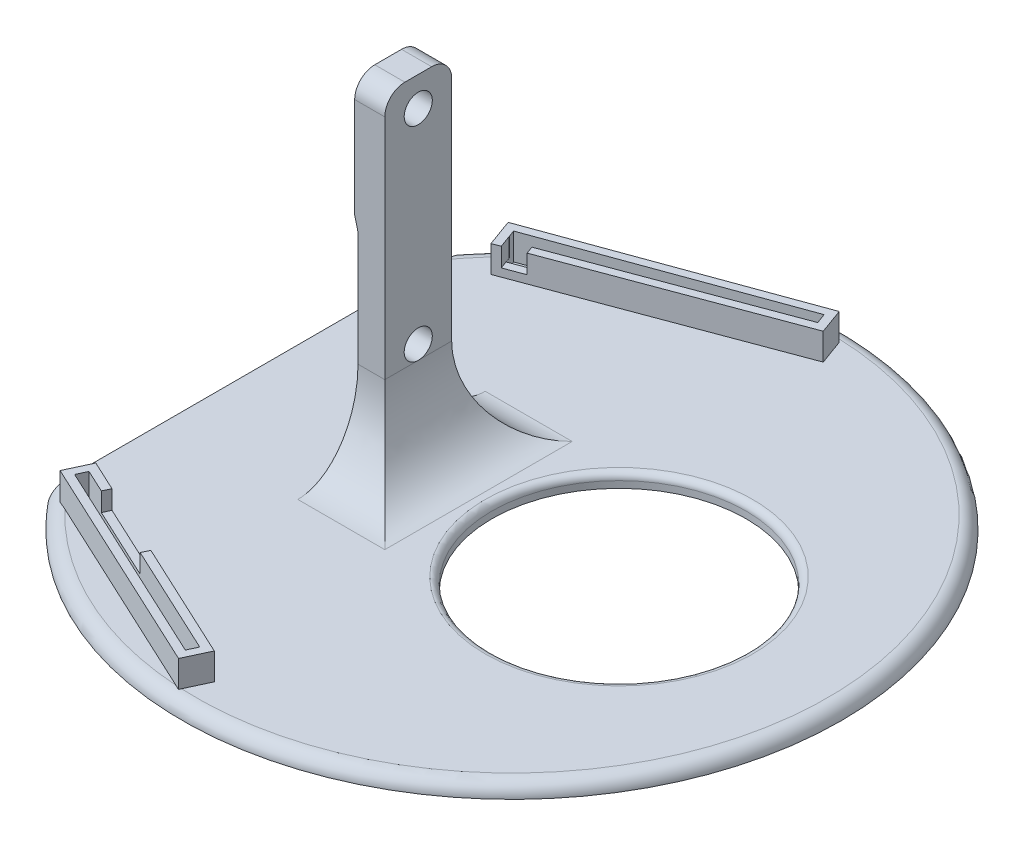
SolidWorks part; units mm, degrees
ref_plane "Front Plane" through (0, 0, 0) normal (0, 0, 1) x (1, 0, 0)
ref_plane "Top Plane" through (0, 0, 0) normal (0, 1, 0) x (1, 0, 0)
ref_plane "Right Plane" through (0, 0, 0) normal (1, 0, 0) x (0, 0, -1)
sketch "Sketch1" plane through (0, 0, 0) normal (0, 1, 0) x (1, 0, 0)
  line L0 (-38, -31.3299) -> (-38, 31.3299)
  arc A0 (-38, -31.3299) -> (-38, 31.3299) centre (0, 0) ccw
  circle A1 centre (16, 0) radius 19
  dimension "D1" = 98.5
  dimension "D2" = 38
  dimension "D3" = 16
  dimension "D4" = 38
extrude "Boss-Extrude1" add sketch "Sketch1" along normal blind 2
sketch "Sketch2" plane through (0, 2, 0) normal (0, 1, 0) x (1, 0, 0)
  line L0 (-38, 31.3299) -> (-38, -31.3299) construction
  line L1 (-18, -5) -> (-14, -5)
  line L2 (-18, -5) -> (-18, 5)
  line L3 (-18, 5) -> (-14, 5)
  line L4 (-14, -5) -> (-14, 5)
  arc A0 (-38, -31.3299) -> (-38, 31.3299) centre (0, 0) ccw construction
  dimension "D1" = 4
  dimension "D2" = 10
  dimension "D3" = 5
  dimension "D4" = 20
extrude "Boss-Extrude2" add sketch "Sketch2" along normal blind 50
sketch "Sketch3" plane through (0, 2, 0) normal (0, 1, 0) x (1, 0, 0)
  line L0 (-0.6321, -43.8483) -> (-2.331, -47.4917)
  line L1 (-2.2268, -44.4288) -> (-2.9115, -45.897)
  line L2 (-2.2268, -44.4288) -> (-33.2226, -29.9752)
  line L3 (-33.2226, -29.9752) -> (-33.9072, -31.4434)
  line L4 (-2.9115, -45.897) -> (-33.9072, -31.4434)
  line L5 (-2.331, -47.4917) -> (-35.5019, -32.0239)
  line L6 (-33.803, -28.3805) -> (-35.5019, -32.0239)
  line L7 (-0.6321, -43.8483) -> (-33.803, -28.3805)
  dimension "D1" = 34.2
  dimension "D2" = 1.62
  dimension "D3" = 1.2
extrude "Boss-Extrude3" add sketch "Sketch3" along normal blind 4
sketch "Sketch4" plane through (0, 2, 0) normal (0, 1, 0) x (1, 0, 0)
  line L0 (-32.6789, 29.5446) -> (3.4893, 43.0265)
  line L1 (-31.9649, 31.0914) -> (1.9552, 43.7353)
  line L2 (-31.9649, 31.0914) -> (-32.6079, 32.858)
  line L3 (-32.6079, 32.858) -> (1.4089, 45.2391)
  line L4 (1.9552, 43.7353) -> (1.4089, 45.2391)
  line L5 (3.4893, 43.0265) -> (2.1269, 46.7775)
  line L6 (-34.146, 33.5752) -> (2.1269, 46.7775)
  line L7 (-32.6789, 29.5446) -> (-34.146, 33.5752)
  dimension "D1" = 36.2
  dimension "D2" = 1.6
  dimension "D3" = 1.2
extrude "Boss-Extrude4" add sketch "Sketch4" along normal blind 4
sketch "Sketch10" plane through (-18, 0, 0) normal (-1, 0, 0) x (0, 0, 1)
  line L0 (5, 52) -> (5, 2) construction
  line L1 (-5, 52) -> (5, 52)
  line L2 (-5, 52) -> (-5, 34)
  line L3 (-5, 34) -> (5, 34)
  line L4 (5, 52) -> (5, 34)
  dimension "D1" = 18
extrude "Boss-Extrude6" add sketch "Sketch10" along normal blind 0.5
sketch "Sketch5" plane through (-14, 0, 0) normal (1, 0, 0) x (0, 0, -1)
  line L0 (-5, 52) -> (-5, 2) construction
  line L1 (-5, 2) -> (5, 2) construction
  circle A0 centre (0, 17.1) radius 2.1
  circle A1 centre (0, 47.6) radius 2.1
  dimension "D1" = 4.2
  dimension "D2" = 5
  dimension "D3" = 15.1
  dimension "D4" = 2
extrude "Cut-Extrude1" cut sketch "Sketch5" against normal blind 10
fillet "Fillet2" radius 9 3 edges at (-16, 2, 5) (-16, 2, -5) (-14, 2, 0) second distance 13 first distance on face at (-18.067, 2, 37.9361)
fillet "Fillet3" radius 3 2 edges at (-16.25, 52, 5) (-16.25, 52, -5)
fillet "Fillet4" radius 1 1 edges at (16, 2, 19)
fillet "Fillet5" radius 2 1 edges at (49.25, 2, 0)
sketch "Sketch6" plane through (-16.9078, 0, 36.2589) normal (0.4226, 0, -0.9063) x (-0.9063, 0, -0.4226)
  line L0 (-17.9582, 6) -> (18.6418, 6) construction
  line L1 (13.6418, 6) -> (1.6418, 6)
  line L2 (13.6418, 6) -> (13.6418, 3.2)
  line L3 (13.6418, 3.2) -> (1.6418, 3.2)
  line L4 (1.6418, 6) -> (1.6418, 3.2)
  line L5 (-17.9582, 2) -> (18.6418, 2) construction
  dimension "D1" = 5
  dimension "D2" = 12
  dimension "D3" = 1.2
extrude "Cut-Extrude2" cut sketch "Sketch6" against normal blind 2
sketch "Sketch7" plane through (-13.656, 0, -36.6355) normal (0.3493, 0, 0.937) x (0.937, 0, -0.3493)
  line L0 (-20.3015, 6) -> (18.2978, 6) construction
  line L1 (-19.1015, 6) -> (-16.1015, 6)
  line L2 (-19.1015, 6) -> (-19.1015, 3.2)
  line L3 (-19.1015, 3.2) -> (-16.1015, 3.2)
  line L4 (-16.1015, 6) -> (-16.1015, 3.2)
  line L5 (-20.3015, 2) -> (18.2978, 2) construction
  dimension "D1" = 3
  dimension "D2" = 1.2
  dimension "D3" = 1.2
extrude "Cut-Extrude3" cut sketch "Sketch7" against normal blind 2
fillet "Fillet6" radius 2 1 edges at (-18, 34, 0) second distance 0.5 conic rho 0.05 first distance on face at (-18, 17.1, -2.1)
